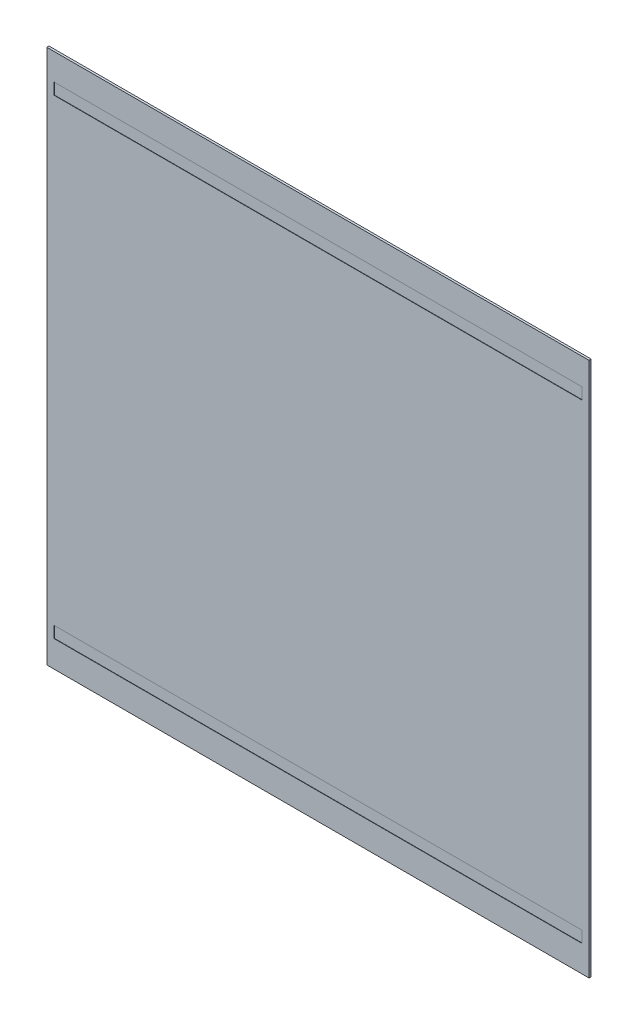
SolidWorks part; units mm, degrees
ref_plane "Front" through (0, 0, 0) normal (0, 0, 1) x (1, 0, 0)
ref_plane "Top" through (0, 0, 0) normal (0, 1, 0) x (1, 0, 0)
ref_plane "Right" through (0, 0, 0) normal (1, 0, 0) x (0, 0, -1)
sketch "Sketch1" plane through (0, 0, 0) normal (0, 0, 1) x (1, 0, 0)
  line L5 (-37.5, 37) -> (37.5, 37)
  line L6 (-37.5, 37) -> (-37.5, -37)
  line L7 (-37.5, -37) -> (37.5, -37)
  line L8 (37.5, 37) -> (37.5, -37)
extrude "Extrude1" add sketch "Sketch1" along normal blind 0.3
sketch "Sketch2" plane through (0, 0, 0.3) normal (0, 0, 1) x (1, 0, 0)
  line L2 (-36.5125, 33.3375) -> (36.5125, 33.3375)
  line L3 (-36.5125, 33.3375) -> (-36.5125, 31.75)
  line L4 (-36.5125, 31.75) -> (36.5125, 31.75)
  line L6 (36.5125, 33.3375) -> (36.5125, 31.75)
  line L7 (-36.5125, -31.75) -> (36.5125, -31.75)
  line L8 (-36.5125, -31.75) -> (-36.5125, -33.3375)
  line L9 (-36.5125, -33.3375) -> (36.5125, -33.3375)
  line L10 (36.5125, -31.75) -> (36.5125, -33.3375)
extrude "Cut-Extrude1" cut sketch "Sketch2" against normal blind 0.05
